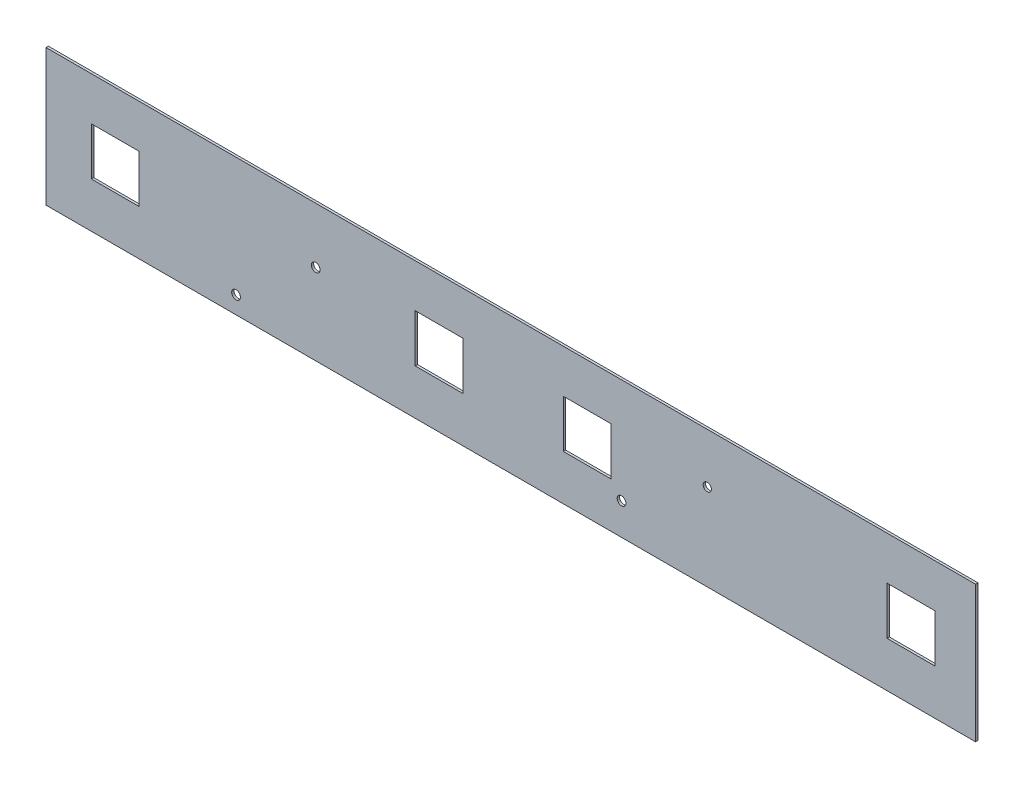
SolidWorks part; units mm, degrees
note: The reader was unsure of these and kept them because the rebuilt part matched: thickness of "Base-Flange1", "Sheet-Metal1", "Sheet-Metal4", "Sheet-Metal5", "Sheet-Metal6", "Sheet-Metal7".
material "ABS"
ref_plane "X-Y Datum" through (0, 0, 0) normal (0, 0, 1) x (1, 0, 0)
ref_plane "X-Z Datum" through (0, 0, 0) normal (0, 1, 0) x (1, 0, 0)
ref_plane "Y-Z Datum" through (0, 0, 0) normal (1, 0, 0) x (0, 0, -1)
sketch "Sketch1" plane through (0, 0, 0) normal (0, 0, 1) x (1, 0, 0)
  line L0 (-350.637, -168.4194) -> (272.9229, -168.4194)
  line L5 (-350.637, -168.4194) -> (-350.637, -90.2559)
  line L6 (-350.637, -90.2559) -> (272.9229, -90.2559)
  line L7 (272.9229, -168.4194) -> (272.9229, -90.2559)
base flange "Base-Flange1" sketch "Sketch1" thickness 1.5875 reverse thickness direction no parameters "D1"=9.525
sketch "Sketch3" plane through (0, 0, 0) normal (0, 0, 1) x (1, 0, 0)
  line L0 (-317.6499, -135.4524) -> (-290.6499, -135.4524) construction
  line L1 (-317.6499, -135.4524) -> (-317.6499, -108.4524) construction
  line L2 (-317.6499, -108.4524) -> (-290.6499, -108.4524) construction
  line L3 (-290.6499, -135.4524) -> (-290.6499, -108.4524) construction
  line L4 (-317.6499, -135.4524) -> (-290.6499, -108.4524) construction
  line L5 (-317.6499, -108.4524) -> (-290.6499, -135.4524) construction
  line L6 (216.1108, -135.4524) -> (243.1108, -135.4524) construction
  line L7 (216.1108, -135.4524) -> (216.1108, -108.4524) construction
  line L8 (216.1108, -108.4524) -> (243.1108, -108.4524) construction
  line L9 (243.1108, -135.4524) -> (243.1108, -108.4524) construction
  line L10 (216.1108, -135.4524) -> (243.1108, -108.4524) construction
  line L11 (216.1108, -108.4524) -> (243.1108, -135.4524) construction
  line L12 (-1.1075, -135.4524) -> (25.8925, -135.4524) construction
  line L13 (-1.1075, -135.4524) -> (-1.1075, -108.4524) construction
  line L14 (-1.1075, -108.4524) -> (25.8925, -108.4524) construction
  line L15 (25.8925, -135.4524) -> (25.8925, -108.4524) construction
  line L16 (-1.1075, -135.4524) -> (25.8925, -108.4524) construction
  line L17 (-1.1075, -108.4524) -> (25.8925, -135.4524) construction
  line L18 (-100.4316, -135.4524) -> (-73.4316, -135.4524) construction
  line L19 (-100.4316, -135.4524) -> (-100.4316, -108.4524) construction
  line L20 (-100.4316, -108.4524) -> (-73.4316, -108.4524) construction
  line L21 (-73.4316, -135.4524) -> (-73.4316, -108.4524) construction
  line L22 (-100.4316, -135.4524) -> (-73.4316, -108.4524) construction
  line L23 (-100.4316, -108.4524) -> (-73.4316, -135.4524) construction
  line L24 (272.9229, -90.2559) -> (100.0301, -90.2559) construction
  line L25 (272.9229, -90.2559) -> (272.9229, -148.8843) construction
  line L26 (272.9229, -148.8843) -> (100.0301, -148.8843) construction
  line L27 (100.0301, -90.2559) -> (100.0301, -148.8843) construction
  line L28 (-320.1899, -137.9924) -> (-288.1099, -137.9924)
  line L29 (-288.1099, -137.9924) -> (-288.1099, -105.9124)
  line L30 (-320.1899, -105.9124) -> (-288.1099, -105.9124)
  line L31 (-320.1899, -137.9924) -> (-320.1899, -105.9124)
  line L32 (-102.9716, -137.9924) -> (-70.8916, -137.9924)
  line L33 (-70.8916, -137.9924) -> (-70.8916, -105.9124)
  line L34 (-102.9716, -105.9124) -> (-70.8916, -105.9124)
  line L35 (-102.9716, -137.9924) -> (-102.9716, -105.9124)
  line L36 (-3.6475, -137.9924) -> (28.4325, -137.9924)
  line L37 (28.4325, -137.9924) -> (28.4325, -105.9124)
  line L38 (-3.6475, -105.9124) -> (28.4325, -105.9124)
  line L39 (-3.6475, -137.9924) -> (-3.6475, -105.9124)
  line L40 (213.5708, -137.9924) -> (245.6508, -137.9924)
  line L41 (245.6508, -137.9924) -> (245.6508, -105.9124)
  line L42 (213.5708, -105.9124) -> (245.6508, -105.9124)
  line L43 (213.5708, -137.9924) -> (213.5708, -105.9124)
  line L44 (-350.637, -168.4194) -> (272.9229, -168.4194) construction
  line L45 (272.9229, -168.4194) -> (272.9229, -90.2559) construction
  circle A0 centre (92.9145, -110.3691) radius 2.75
  circle A1 centre (35.3919, -147.1475) radius 2.921
  circle A2 centre (-169.7713, -114.1653) radius 2.921
  circle A3 centre (-223.1492, -156.7365) radius 2.921
  circle A4 centre (-197.6534, -133.8628) radius 34.1381 construction
  circle A5 centre (64.1532, -128.7583) radius 34.1376 construction
  point P0 (-304.1499, -121.9524)
  point P5 (229.6108, -121.9524)
  point P10 (12.3925, -121.9524)
  point P15 (-86.9316, -121.9524)
  point P32 (272.9229, -90.2559)
  point P61 (-170.1078, -114.1653)
  dimension "D2" = 68.2752
  dimension "D3" = 68.2752
  dimension "D4" = 68.2752
  dimension "D1" = 27
  dimension "D5" = 27
  dimension "D6" = 72.3242
  dimension "D7" = 39.6611
  dimension "D8" = 208.7696
  dimension "D9" = 27
  dimension "D10" = 27
  dimension "D11" = 190.2183
  dimension "D12" = 2.54
  dimension "D13" = 2.54
  dimension "D14" = 2.54
  dimension "D15" = 2.54
extrude "Cut-Extrude3" cut sketch "Sketch3" against normal through all normal cut yes
sketch "Sketch4" plane through (0, 0, 0) normal (0, 0, 1) x (1, 0, 0)
  line L0 (272.9229, -90.2559) -> (-38.8571, -90.2559)
  line L1 (272.9229, -90.2559) -> (272.9229, -168.7239)
  line L2 (272.9229, -168.7239) -> (-38.8571, -168.7239)
  line L3 (-38.8571, -90.2559) -> (-38.8571, -168.7239)
  point P4 (272.9229, -90.2559)
extrude "Cut-Extrude4" [suppressed] cut sketch "Sketch4" against normal through all
sketch "Sketch5" plane through (0, 0, 0) normal (0, 0, 1) x (1, 0, 0)
  line L0 (272.9229, -90.2559) -> (-35.6821, -90.2559)
  line L1 (272.9229, -90.2559) -> (272.9229, -168.7239)
  line L2 (272.9229, -168.7239) -> (-35.6821, -168.7239)
  line L3 (-35.6821, -90.2559) -> (-35.6821, -168.7239)
  point P4 (272.9229, -90.2559)
extrude "Cut-Extrude5" [suppressed] cut sketch "Sketch5" against normal through all flip side to cut
sketch "Sketch6" plane through (0, 0, 0) normal (0, 0, 1) x (1, 0, 0)
  line L1 (-350.637, -90.2559) -> (272.9229, -90.2559)
  line L2 (-350.637, -90.2559) -> (-350.637, -76.8447)
  line L3 (-350.637, -76.8447) -> (272.9229, -76.8447)
  line L4 (272.9229, -90.2559) -> (272.9229, -76.8447)
extrude "Boss-Extrude1" add sketch "Sketch6" against normal through all
sketch "Bend-Lines1" [suppressed] plane through (0, 0, 0) normal (0, 1, 0) x (1, 0, 0)
sketch "Bounding-Box1" [suppressed] plane through (0, 0, 0) normal (0, 1, 0) x (1, 0, 0)
sheet metal parameters "Sheet-Metal1" thickness 1.5875 parameters "D1"=9.525
flat pattern "Flat-Pattern1" [suppressed]
sketch "Bend-Lines2" plane through (0, 0, 0) normal (0, 1, 0) x (1, 0, 0)
sketch3d "Bounding-Box2" [suppressed]
  line L0 (-350.637, -168.4194, 0) -> (272.9229, -168.4194, 0) construction
  line L1 (-350.637, -90.2559, 0) -> (272.9229, -90.2559, 0) construction
  line L2 (-350.637, -168.4194, 0) -> (-350.637, -90.2559, 0) construction
  line L3 (272.9229, -168.4194, 0) -> (272.9229, -90.2559, 0) construction
sheet metal parameters "Sheet-Metal4" thickness 1.5875 parameters "D1"=9.525
flat pattern "Flat-Pattern1"
sketch "Bend-Lines2" plane through (0, 0, 0) normal (0, 1, 0) x (1, 0, 0)
sketch3d "Bounding-Box2" [suppressed]
  line L0 (-350.637, -168.4194, 0) -> (272.9229, -168.4194, 0) construction
  line L1 (-350.637, -90.2559, 0) -> (272.9229, -90.2559, 0) construction
  line L2 (-350.637, -168.4194, 0) -> (-350.637, -90.2559, 0) construction
  line L3 (272.9229, -168.4194, 0) -> (272.9229, -90.2559, 0) construction
sheet metal parameters "Sheet-Metal5" thickness 1.5875 parameters "D1"=9.525
flat pattern "Flat-Pattern1"
sketch "Bend-Lines2" plane through (0, 0, 0) normal (0, 1, 0) x (1, 0, 0)
sketch3d "Bounding-Box2" [suppressed]
  line L0 (-350.637, -168.4194, 0) -> (-38.8571, -168.4194, 0) construction
  line L1 (-350.637, -90.2559, 0) -> (-38.8571, -90.2559, 0) construction
  line L2 (-350.637, -168.4194, 0) -> (-350.637, -90.2559, 0) construction
  line L3 (-38.8571, -168.4194, 0) -> (-38.8571, -90.2559, 0) construction
sheet metal parameters "Sheet-Metal6" thickness 1.5875 parameters "D1"=9.525
flat pattern "Flat-Pattern1"
sketch "Bend-Lines2" plane through (0, 0, 0) normal (0, 1, 0) x (1, 0, 0)
sketch3d "Bounding-Box2" [suppressed]
  line L0 (-35.6821, -168.4194, 0) -> (272.9229, -168.4194, 0) construction
  line L1 (-35.6821, -90.2559, 0) -> (272.9229, -90.2559, 0) construction
  line L2 (-35.6821, -168.4194, 0) -> (-35.6821, -90.2559, 0) construction
  line L3 (272.9229, -168.4194, 0) -> (272.9229, -90.2559, 0) construction
sheet metal parameters "Sheet-Metal7" thickness 1.5875 parameters "D1"=9.525
flat pattern "Flat-Pattern1"
sketch "Bend-Lines2" plane through (0, 0, 0) normal (0, 1, 0) x (1, 0, 0)
sketch3d "Bounding-Box2" [suppressed]
  line L0 (-350.637, -168.4194, 0) -> (272.9229, -168.4194, 0) construction
  line L1 (-350.637, -76.8447, 0) -> (272.9229, -76.8447, 0) construction
  line L2 (-350.637, -168.4194, 0) -> (-350.637, -76.8447, 0) construction
  line L3 (272.9229, -168.4194, 0) -> (272.9229, -76.8447, 0) construction
